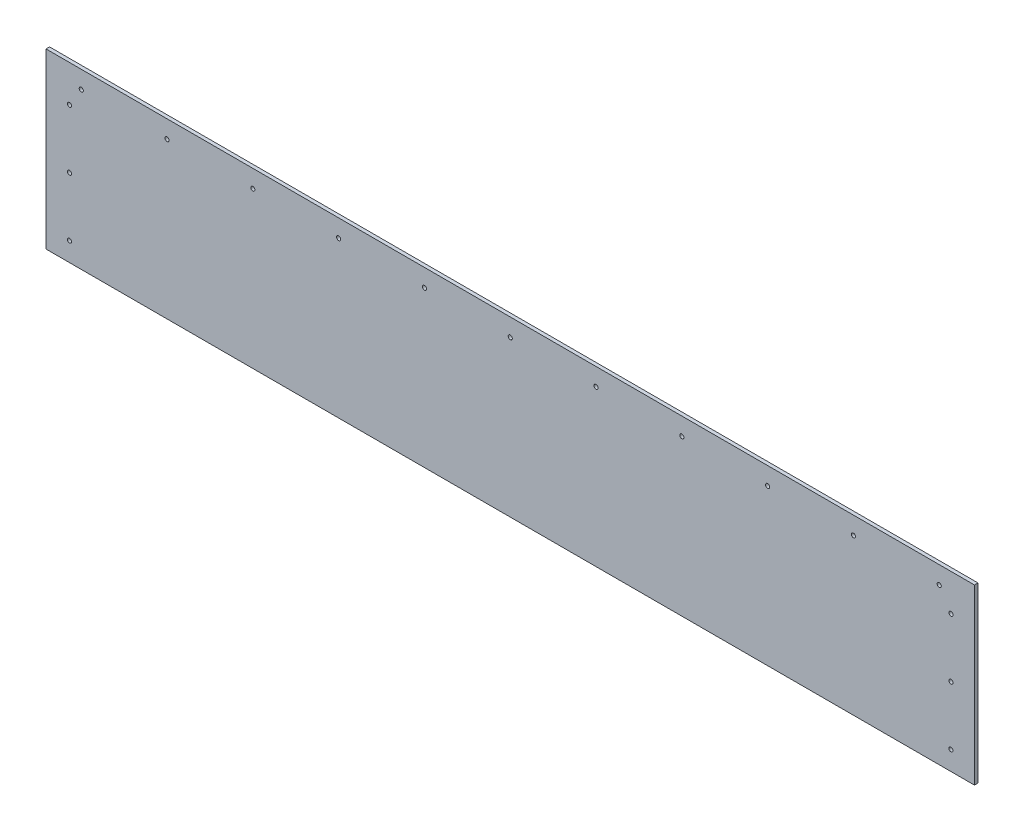
SolidWorks part; units mm, degrees
material "AISI 304"
ref_plane "Front Plane" through (0, 0, 0) normal (0, 0, 1) x (1, 0, 0)
ref_plane "Top Plane" through (0, 0, 0) normal (0, 1, 0) x (1, 0, 0)
ref_plane "Right Plane" through (0, 0, 0) normal (1, 0, 0) x (0, 0, -1)
sketch "Sketch1" plane through (0, 0, 0) normal (0, 0, 1) x (1, 0, 0)
  line L0 (859.9855, -5) -> (-859.9855, -5)
  arc A0 (-859.9855, -5) -> (859.9855, -5) centre (0, 0) ccw
  dimension "D1" = 1720
  dimension "D2" = 5
base flange "Base-Flange1" sketch "Sketch1" thickness 6 reverse thickness direction no parameters "D1"=0
sketch "Sketch6" plane through (0, 0, 0) normal (0, 0, 1) x (1, 0, 0)
  line L1 (-1073.4129, -300) -> (878.954, -300)
  line L2 (-1073.4129, -300) -> (-1073.4129, -935.2323)
  line L3 (-1073.4129, -935.2323) -> (878.954, -935.2323)
  line L4 (878.954, -300) -> (878.954, -935.2323)
  dimension "D1" = 300
extrude "Cut-Extrude1" cut sketch "Sketch6" against normal blind 10 normal cut yes
sketch "Sketch7" plane through (0, 0, 0) normal (0, 0, 1) x (1, 0, 0)
  line L0 (-859.9855, -5) -> (-789.9855, -5)
  line L1 (859.9855, -5) -> (-859.9855, -5) construction
  line L2 (-789.9855, -5) -> (-789.9855, -300)
  line L3 (805.9777, -300) -> (-805.9777, -300) construction
  line L4 (-789.9855, -300) -> (-805.9777, -300)
  arc A0 (-805.9777, -300) -> (-859.9855, -5) centre (0, 0) cw
  dimension "D1" = 70
extrude "Cut-Extrude2" cut sketch "Sketch7" against normal blind 10 normal cut yes
mirror "Mirror1" about plane through (0, 0, 0) normal (1, 0, 0) of "Cut-Extrude2"
sketch "Sketch8" plane through (0, 0, 0) normal (0, 0, 1) x (1, 0, 0)
  line L0 (789.9855, -5) -> (-789.9855, -5) construction
  circle A0 centre (0, -35) radius 3.5
  dimension "D1" = 7
  dimension "D2" = 30
extrude "Cut-Extrude3" cut sketch "Sketch8" against normal blind 10 normal cut yes
pattern_linear "LPattern1" count 6 spacing 146 along (-1, 0, 0) count 6 spacing 146 along (1, 0, 0) of "Cut-Extrude3"
sketch "Sketch9" plane through (0, 0, -6) normal (0, 0, -1) x (-1, 0, 0)
  line L0 (-789.9855, -300) -> (-789.9855, -5) construction
  line L1 (-789.9855, -5) -> (789.9855, -5) construction
  circle A0 centre (-749.9855, -167.5) radius 3.5
  dimension "D2" = 162.5
  dimension "D3" = 7
  dimension "D1" = 40
extrude "Cut-Extrude4" cut sketch "Sketch9" against normal blind 10 normal cut yes
pattern_linear "LPattern2" count 2 spacing 100 along (0, -1, 0) count 2 spacing 100 along (0, 1, 0) of "Cut-Extrude4"
mirror "Mirror2" about plane through (0, 0, 0) normal (1, 0, 0) of "Cut-Extrude4", "LPattern2"
sketch "Bend-Lines1" [suppressed] plane through (0, 0, 0) normal (0, 1, 0) x (1, 0, 0)
sketch "Bounding-Box1" [suppressed] plane through (0, 0, 0) normal (0, 1, 0) x (1, 0, 0)
sheet metal parameters "Sheet-Metal3" thickness 6 parameters "D1"=0
flat pattern "Flat-Pattern3" [suppressed]
sketch "Bend-Lines2" plane through (0, 0, 0) normal (0, 1, 0) x (1, 0, 0)
sketch3d "Bounding-Box2" [suppressed]
  line L0 (789.9842, -5, 0) -> (-789.9842, -5, 0) construction
  line L1 (789.9842, -789.9999, 0) -> (-789.9842, -789.9999, 0) construction
  line L2 (789.9842, -5, 0) -> (789.9842, -789.9999, 0) construction
  line L3 (-789.9842, -5, 0) -> (-789.9842, -789.9999, 0) construction
sheet metal parameters "Sheet-Metal4" thickness 6 parameters "D1"=0
flat pattern "Flat-Pattern3"
sketch "Bend-Lines2" plane through (0, 0, 0) normal (0, 1, 0) x (1, 0, 0)
sketch3d "Bounding-Box2" [suppressed]
  line L0 (-859.9855, -300, 0) -> (859.9855, -300, 0) construction
  line L1 (-859.9855, -5, 0) -> (859.9855, -5, 0) construction
  line L2 (-859.9855, -300, 0) -> (-859.9855, -5, 0) construction
  line L3 (859.9855, -300, 0) -> (859.9855, -5, 0) construction
sheet metal parameters "Sheet-Metal5" thickness 6 parameters "D1"=0
flat pattern "Flat-Pattern3"
sketch "Bend-Lines2" plane through (0, 0, 0) normal (0, 1, 0) x (1, 0, 0)
sketch3d "Bounding-Box2" [suppressed]
  line L0 (-789.9855, -300, 0) -> (859.9855, -300, 0) construction
  line L1 (-789.9855, -5, 0) -> (859.9855, -5, 0) construction
  line L2 (-789.9855, -300, 0) -> (-789.9855, -5, 0) construction
  line L3 (859.9855, -300, 0) -> (859.9855, -5, 0) construction
sheet metal parameters "Sheet-Metal6" thickness 6 parameters "D1"=0
flat pattern "Flat-Pattern3"
sketch "Bend-Lines2" plane through (0, 0, 0) normal (0, 1, 0) x (1, 0, 0)
sketch3d "Bounding-Box2" [suppressed]
  line L0 (-789.9855, -290, 0) -> (789.9855, -290, 0) construction
  line L1 (-789.9855, -5, 0) -> (789.9855, -5, 0) construction
  line L2 (-789.9855, -290, 0) -> (-789.9855, -5, 0) construction
  line L3 (789.9855, -290, 0) -> (789.9855, -5, 0) construction
sheet metal parameters "Sheet-Metal7" thickness 6 parameters "D1"=0
flat pattern "Flat-Pattern3"
sketch "Bend-Lines2" plane through (0, 0, 0) normal (0, 1, 0) x (1, 0, 0)
sketch3d "Bounding-Box2" [suppressed]
  line L0 (-789.9855, -290, 0) -> (789.9855, -290, 0) construction
  line L1 (-789.9855, -5, 0) -> (789.9855, -5, 0) construction
  line L2 (-789.9855, -290, 0) -> (-789.9855, -5, 0) construction
  line L3 (789.9855, -290, 0) -> (789.9855, -5, 0) construction
sheet metal parameters "Sheet-Metal8" thickness 6 parameters "D1"=0
flat pattern "Flat-Pattern3"
sketch "Bend-Lines2" plane through (0, 0, 0) normal (0, 1, 0) x (1, 0, 0)
sketch3d "Bounding-Box2" [suppressed]
  line L0 (-789.9855, -300, 0) -> (789.9855, -300, 0) construction
  line L1 (-789.9855, -5, 0) -> (789.9855, -5, 0) construction
  line L2 (-789.9855, -300, 0) -> (-789.9855, -5, 0) construction
  line L3 (789.9855, -300, 0) -> (789.9855, -5, 0) construction
sheet metal parameters "Sheet-Metal9" thickness 6 parameters "D1"=0
flat pattern "Flat-Pattern3"
sketch "Bend-Lines2" plane through (0, 0, 0) normal (0, 1, 0) x (1, 0, 0)
sketch3d "Bounding-Box2" [suppressed]
  line L0 (-789.9855, -300, 0) -> (789.9855, -300, 0) construction
  line L1 (-789.9855, -5, 0) -> (789.9855, -5, 0) construction
  line L2 (-789.9855, -300, 0) -> (-789.9855, -5, 0) construction
  line L3 (789.9855, -300, 0) -> (789.9855, -5, 0) construction
sheet metal parameters "Sheet-Metal10" thickness 6 parameters "D1"=0
flat pattern "Flat-Pattern3"
sketch "Bend-Lines2" plane through (0, 0, 0) normal (0, 1, 0) x (1, 0, 0)
sketch3d "Bounding-Box2" [suppressed]
  line L0 (-789.9855, -300, 0) -> (789.9855, -300, 0) construction
  line L1 (-789.9855, -5, 0) -> (789.9855, -5, 0) construction
  line L2 (-789.9855, -300, 0) -> (-789.9855, -5, 0) construction
  line L3 (789.9855, -300, 0) -> (789.9855, -5, 0) construction
sheet metal parameters "Sheet-Metal11" thickness 6 parameters "D1"=0
flat pattern "Flat-Pattern3"
sketch "Bend-Lines2" plane through (0, 0, 0) normal (0, 1, 0) x (1, 0, 0)
sketch3d "Bounding-Box2" [suppressed]
  line L0 (-789.9855, -300, 0) -> (789.9855, -300, 0) construction
  line L1 (-789.9855, -5, 0) -> (789.9855, -5, 0) construction
  line L2 (-789.9855, -300, 0) -> (-789.9855, -5, 0) construction
  line L3 (789.9855, -300, 0) -> (789.9855, -5, 0) construction
